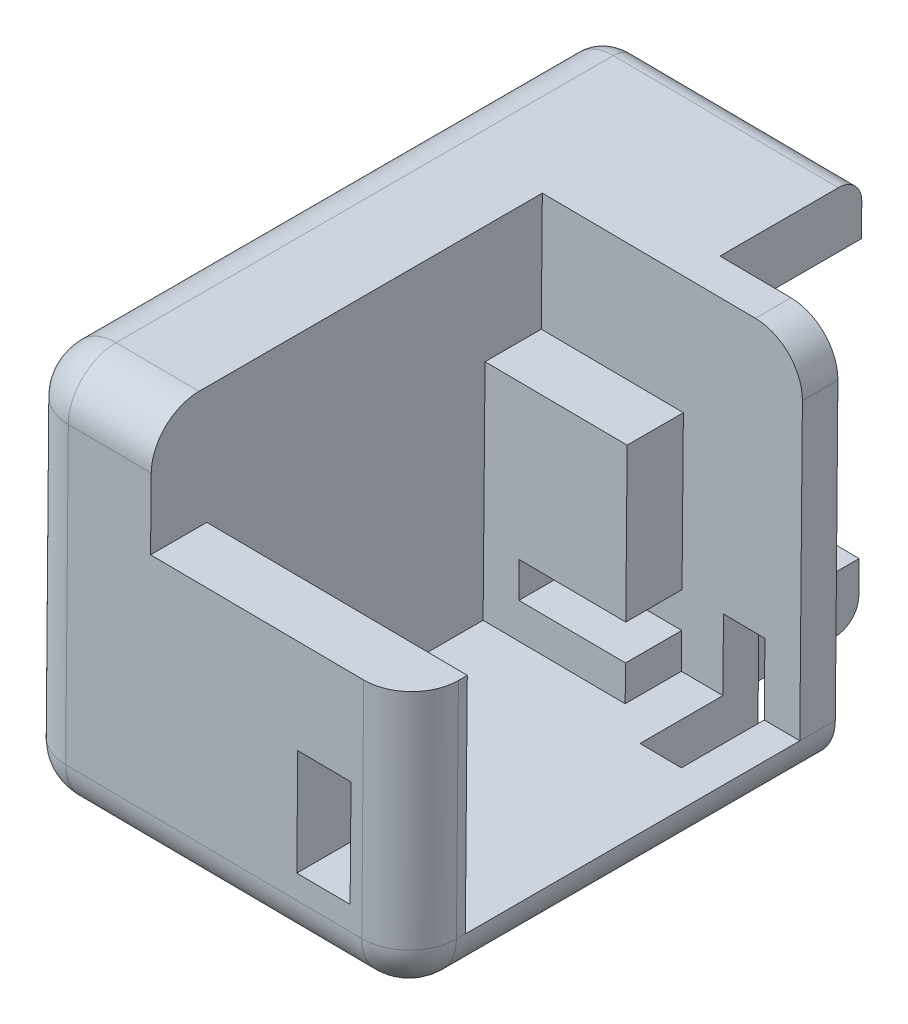
SolidWorks part; units mm, degrees
ref_plane "Plan de face" through (0, 0, 0) normal (0, 0, 1) x (1, 0, 0)
ref_plane "Plan de dessus" through (0, 0, 0) normal (0, 1, 0) x (1, 0, 0)
ref_plane "Plan de droite" through (0, 0, 0) normal (1, 0, 0) x (0, 0, -1)
sketch "Esquisse1" plane through (-30.7505, -23.4954, 0) normal (0, 0, -1) x (-1, 0, 0)
  line L9 (-9.3635, -30.8193) -> (-9.3635, 2.1807)
  line L23 (-32.3635, -1.8193) -> (-32.3635, -26.8193)
  line L24 (-28.3635, -30.8193) -> (-9.3635, -30.8193)
  line L29 (-28.3635, 2.1807) -> (-9.3635, 2.1807)
  arc A2 (-32.3635, -26.8193) -> (-28.3635, -30.8193) centre (-28.3635, -26.8193) ccw
  arc A3 (-28.3635, 2.1807) -> (-32.3635, -1.8193) centre (-28.3635, -1.8193) ccw
  dimension "D2" = 4
  dimension "D1" = 33
  dimension "D4" = 23
extrude "Boss.-Extru.1" add sketch "Esquisse1" along normal blind 15
sketch "Esquisse2" plane through (0, 0, -15) normal (0, 0, -1) x (-1, 0, 0)
  line L2 (21.387, -49.5647) -> (2.387, -49.5647)
  line L3 (2.387, -49.5647) -> (2.387, -26.0647)
  line L4 (2.387, -26.0647) -> (21.387, -26.0647)
  line L5 (21.387, -26.0647) -> (21.387, -49.5647)
  line L11 (-1.613, -25.3147) -> (-1.613, -50.3147) construction
  line L12 (16.4494, -54.3147) -> (16.4494, -49.5647) construction
  line L13 (2.387, -54.3147) -> (21.387, -54.3147) construction
  line L14 (16.4494, -26.0647) -> (16.4494, -21.3147) construction
  line L15 (21.387, -21.3147) -> (2.387, -21.3147) construction
  dimension "D1" = 19
  dimension "D2" = 4
  dimension "D3" = 23.5
extrude "Enlèv. mat.-Extru.1" cut sketch "Esquisse2" against normal blind 12
sketch "Esquisse6" plane through (0, 0, -15) normal (0, 0, -1) x (-1, 0, 0)
  line L0 (21.387, -26.0647) -> (2.387, -26.0647) construction
  line L1 (5.387, -26.0647) -> (8.387, -26.0647)
  line L2 (5.387, -26.0647) -> (5.387, -21.3147)
  line L3 (5.387, -21.3147) -> (8.387, -21.3147)
  line L4 (8.387, -26.0647) -> (8.387, -21.3147)
  line L5 (21.387, -21.3147) -> (2.387, -21.3147) construction
  line L6 (2.387, -26.0647) -> (2.387, -49.5647) construction
  dimension "D1" = 3
  dimension "D2" = 6
extrude "Enlèv. mat.-Extru.3" cut sketch "Esquisse6" against normal blind 9
sketch "Esquisse4" plane through (0, 0, 0) normal (0, 0, 1) x (1, 0, 0)
  line L0 (-21.387, -54.3147) -> (-21.387, -21.3147)
  line L1 (-2.387, -54.3147) -> (-21.387, -54.3147) construction
  line L2 (-21.387, -21.3147) -> (-2.387, -21.3147) construction
  line L3 (-21.387, -21.3147) -> (-2.387, -21.3147)
  line L4 (1.613, -25.3147) -> (1.613, -50.3147)
  line L5 (-2.387, -54.3147) -> (-21.387, -54.3147)
  line L6 (1.613, -25.3147) -> (1.613, -50.3147) construction
  arc A2 (-2.387, -21.3147) -> (1.613, -25.3147) centre (-2.387, -25.3147) cw
  arc A3 (-2.387, -54.3147) -> (1.613, -50.3147) centre (-2.387, -50.3147) ccw
  dimension "D2" = 4
extrude "Boss.-Extru.2" add sketch "Esquisse4" along normal blind 33
sketch "Esquisse5" plane through (-21.387, 0, 0) normal (-1, 0, 0) x (0, 0, 1)
  line L0 (0, -44.3147) -> (4.75, -44.3147)
  line L2 (28.25, -44.3147) -> (28.25, -25.3147)
  line L3 (28.25, -25.3147) -> (4.75, -25.3147)
  line L4 (4.75, -25.3147) -> (4.75, -44.3147)
  line L5 (28.25, -44.3147) -> (33, -44.3147)
  line L6 (33, -54.3147) -> (33, -21.3147) construction
  line L7 (33, -44.3147) -> (33, -54.3147)
  line L8 (33, -54.3147) -> (0, -54.3147)
  line L9 (0, -54.3147) -> (0, -44.3147)
  line L10 (33, -21.3147) -> (-15, -21.3147) construction
  dimension "D1" = 4
  dimension "D2" = 23.5
  dimension "D3" = 19
  dimension "D4" = 33
extrude "Enlèv. mat.-Extru.2" cut sketch "Esquisse5" against normal blind 12
sketch "Esquisse7" plane through (-21.387, 0, 0) normal (-1, 0, 0) x (0, 0, 1)
  line L1 (4.75, -28.3147) -> (0, -28.3147)
  line L2 (4.75, -28.3147) -> (4.75, -31.3147)
  line L3 (4.75, -31.3147) -> (0, -31.3147)
  line L4 (0, -28.3147) -> (0, -31.3147)
  line L6 (28.25, -25.3147) -> (4.75, -25.3147) construction
  line L7 (4.75, -25.3147) -> (4.75, -44.3147) construction
  line L8 (0, -44.3147) -> (0, -54.3147) construction
  dimension "D1" = 3
  dimension "D2" = 6
extrude "Enlèv. mat.-Extru.4" cut sketch "Esquisse7" against normal blind 9
sketch "Esquisse9" plane through (-21.387, 0, 0) normal (-1, 0, 0) x (0, 0, 1)
  line L0 (28.25, -44.3147) -> (33, -44.3147)
  line L1 (33, -44.3147) -> (33, -21.3147)
  line L2 (33, -21.3147) -> (-3, -21.3147)
  line L3 (-15, -21.3147) -> (33, -21.3147) construction
  line L4 (-3, -21.3147) -> (-3, -54.3147)
  line L5 (-15, -54.3147) -> (0, -54.3147) construction
  line L6 (-3, -54.3147) -> (0, -54.3147)
  line L7 (0, -54.3147) -> (0, -25.3147)
  line L14 (0, -25.3147) -> (28.25, -25.3147)
  line L15 (28.25, -25.3147) -> (28.25, -44.3147)
extrude "Boss.-Extru.3" add sketch "Esquisse9" along normal blind 10
sketch "Esquisse10" plane through (0, 0, 33) normal (0, 0, 1) x (1, 0, 0)
  line L0 (-31.387, -44.3147) -> (-31.387, -21.3147) construction
  line L1 (-26.387, -36.3147) -> (-21.887, -36.3147)
  line L2 (-26.387, -36.3147) -> (-26.387, -27.3147)
  line L3 (-26.387, -27.3147) -> (-21.887, -27.3147)
  line L4 (-21.887, -36.3147) -> (-21.887, -27.3147)
  line L5 (-2.387, -21.3147) -> (-31.387, -21.3147) construction
  dimension "D1" = 9
  dimension "D2" = 4.5
  dimension "D3" = 5
  dimension "D4" = 6
extrude "Enlèv. mat.-Extru.5" cut sketch "Esquisse10" against normal blind 10
sketch "Esquisse11" plane through (0, 0, -3) normal (0, 0, -1) x (-1, 0, 0)
  line L0 (31.387, -21.3147) -> (21.387, -21.3147) construction
  line L1 (28.387, -21.3147) -> (24.887, -21.3147)
  line L2 (28.387, -21.3147) -> (28.387, -31.3147)
  line L3 (28.387, -31.3147) -> (24.887, -31.3147)
  line L4 (24.887, -21.3147) -> (24.887, -31.3147)
  line L5 (31.387, -21.3147) -> (31.387, -54.3147) construction
  dimension "D1" = 3.5
  dimension "D2" = 10
  dimension "D3" = 3
extrude "Enlèv. mat.-Extru.6" cut sketch "Esquisse11" against normal blind 10
fillet "Congé2" radius 2 6 edges at (-11.887, -54.3147, -15) (0.4414, -53.1431, -15) (1.613, -37.8147, -15) (0.4414, -22.4863, -15) (-3.887, -21.3147, -15) (-14.887, -21.3147, -15)
fillet "Congé3" radius 4 8 edges at (1.613, -37.8147, 33) (-16.887, -21.3147, 33) (-5.887, -54.3147, 33) (0.4414, -22.4863, 33) (0.4414, -53.1431, 33) (-31.387, -32.8147, 33) (-31.387, -21.3147, 15) (-31.387, -54.3147, -1.5)
move or copy body "Corps-Déplacer/Copier1" bodies to move or copy 110 copy no rotation origin (-14.887, -37.8147, 0) rotation axis (0, 0, 1) rotation angle 179.5
